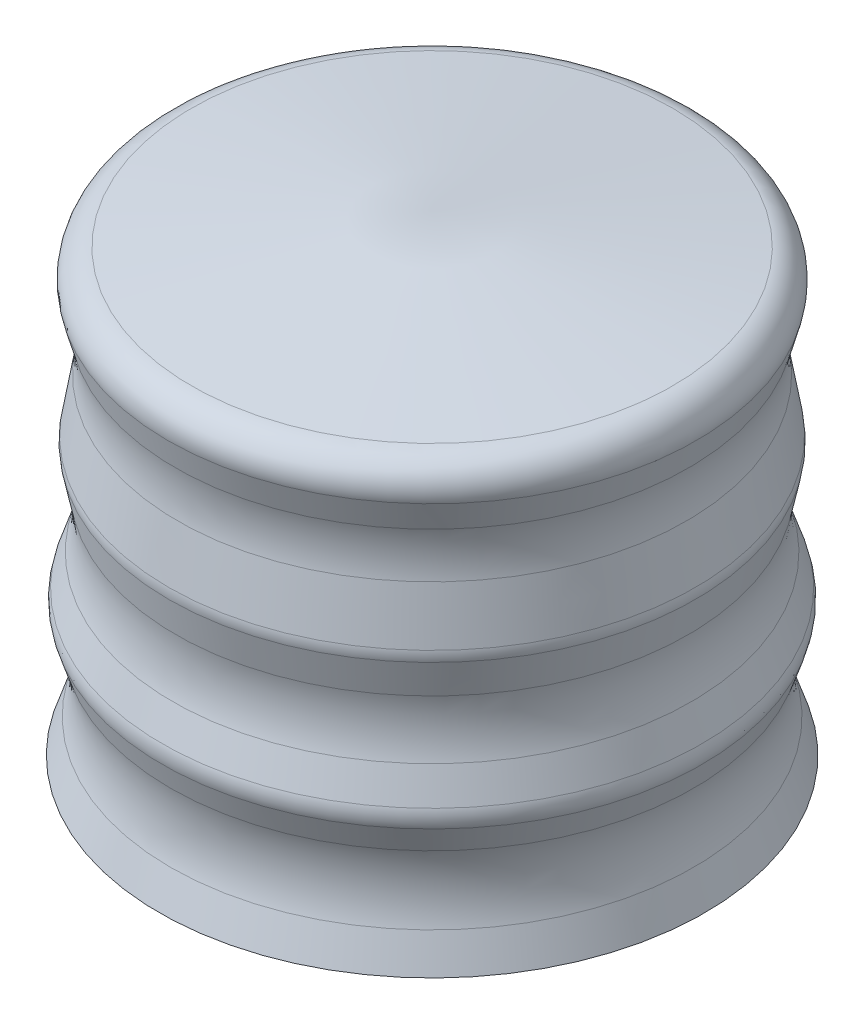
SolidWorks part; units mm, degrees
ref_plane "Front Plane" through (0, 0, 0) normal (0, 0, 1) x (1, 0, 0)
ref_plane "Top Plane" through (0, 0, 0) normal (0, 1, 0) x (1, 0, 0)
ref_plane "Right Plane" through (0, 0, 0) normal (1, 0, 0) x (0, 0, -1)
sketch "Sketch1" plane through (0, 0, 0) normal (1, 0, 0) x (0, 0, -1)
  line L0 (0, 0) -> (4.82, 0)
  line L1 (4.82, 0) -> (4.6216, 0.5951)
  line L2 (4.6216, 1.8049) -> (4.7673, 2.2419)
  line L3 (4.7673, 2.5581) -> (4.5832, 3.1103)
  line L4 (4.5253, 4.1054) -> (4.6506, 4.7068)
  line L5 (4.6538, 4.8938) -> (4.4927, 5.8285)
  line L6 (4.5337, 6.6623) -> (4.6673, 7.1463)
  line L7 (4.2505, 7.775) -> (0, 8.3346)
  line L8 (0, 8.3346) -> (0, 0)
  arc A0 (4.6538, 4.8938) -> (4.6506, 4.7068) centre (4.1611, 4.8088) cw
  arc A1 (4.7673, 2.5581) -> (4.7673, 2.2419) centre (4.293, 2.4) cw
  arc A2 (4.5253, 4.1054) -> (4.5832, 3.1103) centre (6.3981, 3.7152) ccw
  arc A3 (4.6216, 1.8049) -> (4.6216, 0.5951) centre (6.4365, 1.2) ccw
  arc A4 (4.2505, 7.775) -> (4.6673, 7.1463) centre (4.1853, 7.2793) cw
  arc A5 (4.5337, 6.6623) -> (4.4927, 5.8285) centre (6.3779, 6.1536) ccw
  point P3 (4.82, 2.4)
  point P4 (4.67, 4.8)
  point P5 (4.82, 7.7)
  point P6 (4.42, 1.2)
  point P9 (4.42, 3.6)
  point P10 (4.42, 6.25)
  point P17 (4.67, 4.8)
  point P20 (4.82, 2.4)
  point P23 (4.42, 3.6)
  point P26 (4.42, 1.2)
  point P30 (4.82, 7.7)
  point P33 (4.42, 6.25)
  dimension "D10" = 0.5
  dimension "D11" = 1.913
  dimension "D13" = 0.5
  dimension "D14" = 1.913
  dimension "D1" = 4.82
  dimension "D2" = 2.4
  dimension "D3" = 4.8
  dimension "D4" = 7.7
  dimension "D5" = 4.67
  dimension "D6" = 4.42
  dimension "D7" = 1.2
  dimension "D8" = 3.6
  dimension "D9" = 6.25
  dimension "D12" = 7.5
sketch "VerticalRefAxis" plane through (0, 0, 0) normal (1, 0, 0) x (0, 0, -1)
  line L0 (0, 0) -> (0, 11.9929) construction
ref_axis "Axis1" through (0, 0, 0) along (0, 1, 0)
revolve "Revolve1" add sketch "Sketch1" angle 360 about L0
sketch "Sketch3" plane through (0, 0, 0) normal (0, -1, 0) x (1, 0, 0)
  line L0 (1.55, 0.25) -> (3.05, 0.25)
  line L1 (1.55, -0.25) -> (3.05, -0.25)
  circle A0 centre (0, 0) radius 1.3 construction
  circle A1 centre (0, 0) radius 3.3 construction
  arc A2 (1.55, -0.25) -> (1.55, 0.25) centre (1.55, 0) cw
  arc A3 (3.05, -0.25) -> (3.05, 0.25) centre (3.05, 0) ccw
  point P4 (1.3, 0)
  point P5 (3.3, 0)
  point P6 (1.55, 0.25)
  point P7 (1.55, -0.25)
  point P8 (3.05, -0.25)
  point P9 (3.05, 0.25)
  dimension "D2" = 2.6
  dimension "D3" = 6.6
  dimension "D1" = 0.25
  dimension "D4" = 0.25
  dimension "D5" = 0.25
  dimension "D6" = 0.25
extrude "Boss-Extrude1" add sketch "Sketch3" along normal blind 0.25
pattern_circular "CirPattern14" count 4 over 360 about axis through (0, 0, 0) along (0, -1, 0) of "Boss-Extrude1"
fillet "Fillet6" radius 0.25 16 edges at (-2.3, -0.25, -0.25) (-3.3, -0.25, 0) (-2.3, -0.25, 0.25) (-1.3, -0.25, 0) (0.25, -0.25, -2.3) (0, -0.25, -3.3) (-0.25, -0.25, -2.3) (0, -0.25, -1.3) (2.3, -0.25, 0.25) (3.3, -0.25, 0) (2.3, -0.25, -0.25) (1.3, -0.25, 0) (-0.25, -0.25, 2.3) (0, -0.25, 3.3) (0.25, -0.25, 2.3) (0, -0.25, 1.3)
equation "\"D4@Sketch1\"=8.24-0.54"
equation "\"D5@Sketch1\"=9.34/2"
equation "\"D6@Sketch1\"=8.84/2"
equation "\"D7@Sketch1\"=\"D2@Sketch1\"/2"
equation "\"D8@Sketch1\"=(\"D3@Sketch1\"-\"D2@Sketch1\")/2+\"D2@Sketch1\""
equation "\"D9@Sketch1\"=(\"D4@Sketch1\"-\"D3@Sketch1\")/2+\"D3@Sketch1\""
equation "\"D12@Sketch1\"=15/2"
equation "\"D5@Sketch3\"=\"D4@Sketch3\""
equation "\"D6@Sketch3\"=\"D1@Sketch3\""
